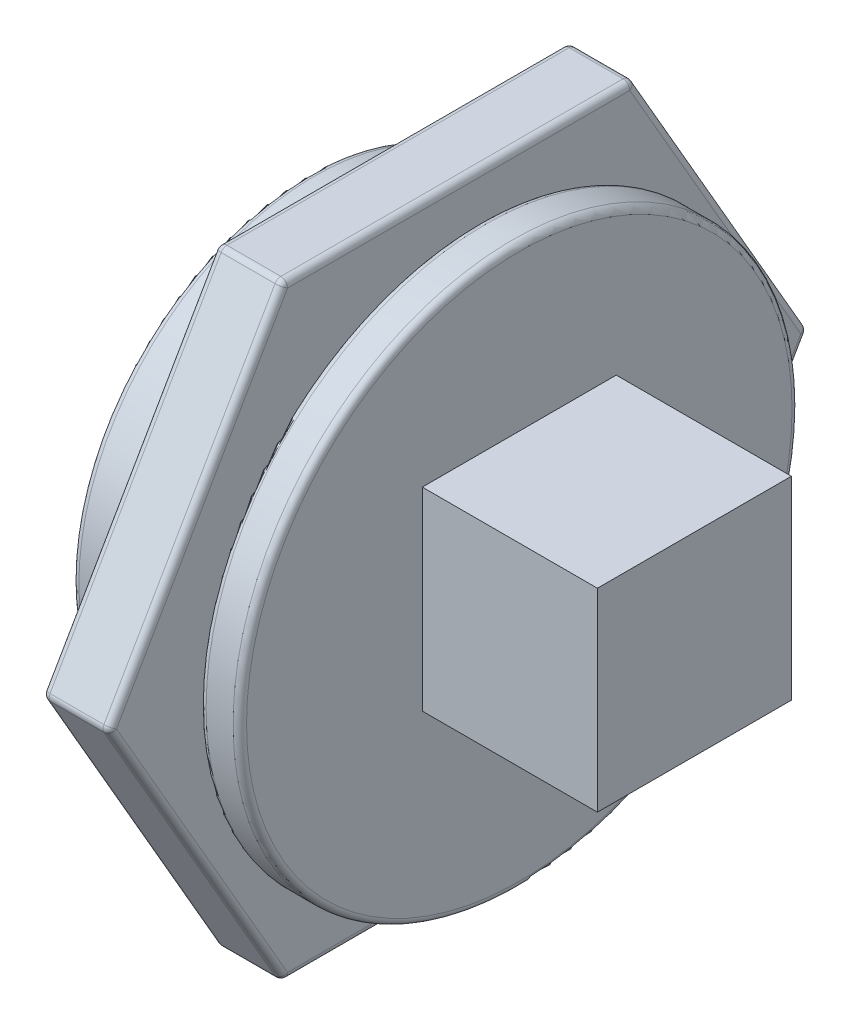
SolidWorks part; units mm, degrees
ref_plane "Plan de face" through (0, 0, 0) normal (0, 0, 1) x (1, 0, 0)
ref_plane "Plan de dessus" through (0, 0, 0) normal (0, 1, 0) x (1, 0, 0)
ref_plane "Plan de droite" through (0, 0, 0) normal (1, 0, 0) x (0, 0, -1)
sketch "Esquisse1" plane through (0, 0, 0) normal (0, 0, 1) x (1, 0, 0)
  line L0 (15.223, 0) -> (-20.2974, 0) construction
  line L1 (-12.7, 0) -> (-12.7, 17.5)
  line L2 (-12.7, 17.5) -> (0, 17.5)
  line L3 (0, 17.5) -> (0, 20.75)
  line L4 (0, 20.75) -> (3, 20.75)
  line L5 (3, 20.75) -> (3, 0)
  line L6 (3, 0) -> (-12.7, 0)
  dimension "D1" = 35
  dimension "D2" = 41.5
  dimension "D3" = 3
  dimension "D4" = 12.7
revolve "Révolution1" add sketch "Esquisse1" angle 360 about L0
sketch "Esquisse2" plane through (0, 0, 0) normal (-1, 0, 0) x (0, 0, 1)
  line L1 (12.9904, -22.5) -> (25.9808, 0)
  line L2 (25.9808, 0) -> (12.9904, 22.5)
  line L3 (12.9904, 22.5) -> (-12.9904, 22.5)
  line L4 (-12.9904, 22.5) -> (-25.9808, 0)
  line L5 (-25.9808, 0) -> (-12.9904, -22.5)
  line L6 (-12.9904, -22.5) -> (12.9904, -22.5)
  circle A0 centre (0, 0) radius 22.5 construction
  dimension "D1" = 45
extrude "Boss.-Extru.1" add sketch "Esquisse2" along normal blind 5 from offset 1.5
sketch "Esquisse3" plane through (3, 0, 0) normal (1, 0, 0) x (0, 0, -1)
  line L1 (-7.2, 8.7) -> (7.2, 8.7)
  line L2 (-7.2, 8.7) -> (-7.2, -5.7)
  line L3 (-7.2, -5.7) -> (7.2, -5.7)
  line L4 (7.2, 8.7) -> (7.2, -5.7)
  line L5 (-7.2, 8.7) -> (7.2, -5.7) construction
  line L6 (-7.2, -5.7) -> (7.2, 8.7) construction
  point P0 (0, 1.5)
  dimension "D1" = 14.4
  dimension "D2" = 5.7
extrude "Boss.-Extru.2" add sketch "Esquisse3" along normal offset from surface (13 mm away) 16 up to face at (0, 0, -17.5)
fillet "Congé1" radius 0.5 23 edges at (-1.5, 0, 17.5) (0, 0, -17.5) (-6.5, -11.25, -19.4856) (-1.5, -11.25, -19.4856) (-4, -22.5, -12.9904) (-6.5, -22.5, 0) (-1.5, -22.5, 0) (-4, -22.5, 12.9904) (-6.5, -11.25, 19.4856) (-1.5, -11.25, 19.4856) (-4, 0, 25.9808) (-6.5, 11.25, 19.4856) (-1.5, 11.25, 19.4856) (-4, 22.5, 12.9904) (-6.5, 22.5, 0) (-1.5, 22.5, 0) (-4, 22.5, -12.9904) (-6.5, 11.25, -19.4856) (-4, 0, -25.9808) (-1.5, 11.25, -19.4856) (-12.7, 0, -17.5) (3, 0, -20.75) (0, 0, -20.75)
sketch "Esquisse4" plane through (-12.7, 0, 0) normal (-1, 0, 0) x (0, 0, 1)
  line L0 (7.2, -5.7) -> (-7.2, -5.7) construction
  line L1 (-7, 8.5) -> (7, 8.5)
  line L2 (-7, 8.5) -> (-7, -5.5)
  line L3 (-7, -5.5) -> (7, -5.5)
  line L4 (7, 8.5) -> (7, -5.5)
  line L5 (-7, 8.5) -> (7, -5.5) construction
  line L6 (-7, -5.5) -> (7, 8.5) construction
  point P0 (0, 1.5)
  dimension "D1" = 14
  dimension "D2" = 0.2
extrude "Enlèv. mat.-Extru.1" cut sketch "Esquisse4" against normal blind 16
